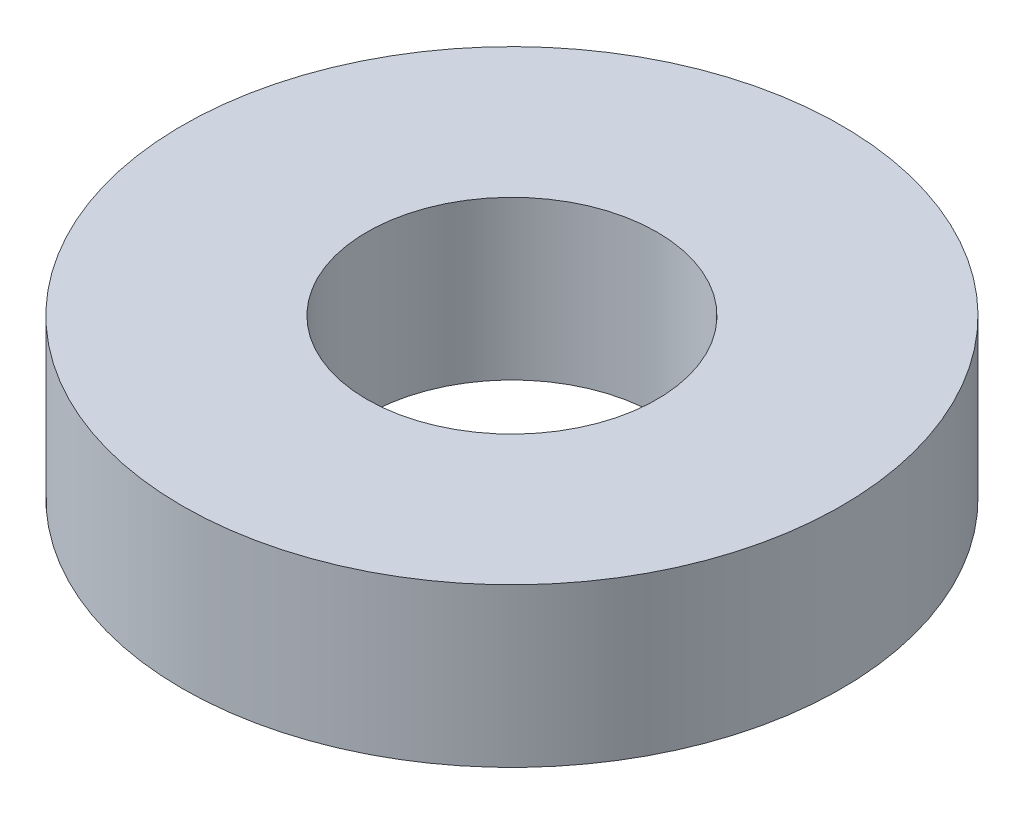
SolidWorks part; units mm, degrees
ref_plane "Front Plane" through (0, 0, 0) normal (0, 0, 1) x (1, 0, 0)
ref_plane "Top Plane" through (0, 0, 0) normal (0, 1, 0) x (1, 0, 0)
ref_plane "Right Plane" through (0, 0, 0) normal (1, 0, 0) x (0, 0, -1)
sketch "Sketch1" plane through (0, 0, 0) normal (0, 1, 0) x (1, 0, 0)
  circle A0 centre (0, 0) radius 62.5
  dimension "FLANGE_OD" = 125
extrude "Boss-Extrude1" add sketch "Sketch1" along normal blind 30
sketch "Sketch2" plane through (0, 0, 0) normal (0, 1, 0) x (1, 0, 0)
  circle A0 centre (0, 0) radius 27.5
  dimension "BORE_D" = 55
extrude "Cut-Extrude1" cut sketch "Sketch2" along normal through all
sketch "Sketch3" plane through (0, 30, 0) normal (0, 1, 0) x (1, 0, 0)
  circle A0 centre (0, 0) radius 20.7072 construction
  circle A1 centre (-20.7072, 0) radius 6.1998
  dimension "BOLT_D" = 12.3995
  dimension "BOLT_PCD" = 41.4143
extrude "Cut-Extrude2" cut sketch "Sketch3" against normal blind 20.4316 rebuild error yes
pattern_circular "CirPattern1" count 4 over 360 rebuild error yes
